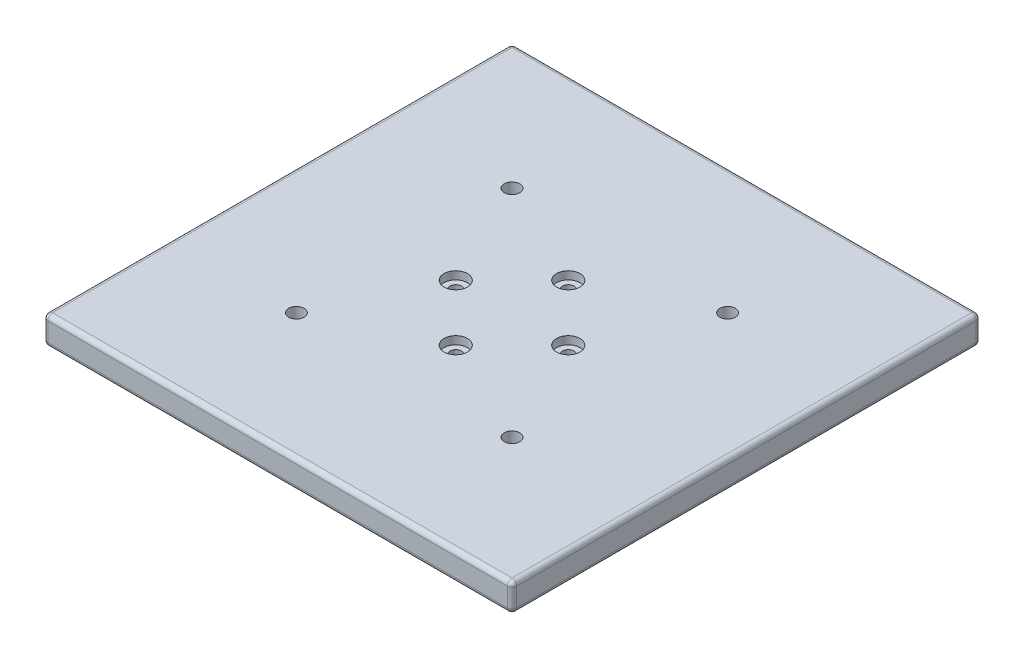
SolidWorks part; units mm, degrees
ref_plane "前视基准面" through (0, 0, 0) normal (0, 0, 1) x (1, 0, 0)
ref_plane "上视基准面" through (0, 0, 0) normal (0, 1, 0) x (1, 0, 0)
ref_plane "右视基准面" through (0, 0, 0) normal (1, 0, 0) x (0, 0, -1)
other "Configuration Table"
sketch "草图1" plane through (0, 0, 0) normal (0, 1, 0) x (1, 0, 0)
  line L1 (-88.6555, 21.1134) -> (11.3445, 21.1134)
  line L2 (-88.6555, 21.1134) -> (-88.6555, -78.8866)
  line L3 (-88.6555, -78.8866) -> (11.3445, -78.8866)
  line L4 (11.3445, 21.1134) -> (11.3445, -78.8866)
  dimension "D1" = 100
extrude "凸台-拉伸1" add sketch "草图1" along normal blind 6
sketch "草图2" plane through (0, 6, 0) normal (0, 1, 0) x (1, 0, 0)
  line L0 (-38.6555, 21.1134) -> (-38.6555, -78.8866) construction
  line L1 (11.3445, 21.1134) -> (-88.6555, 21.1134) construction
  line L2 (-88.6555, -78.8866) -> (11.3445, -78.8866) construction
  line L3 (-88.6555, -28.8866) -> (11.3445, -28.8866) construction
  line L4 (-88.6555, 21.1134) -> (-88.6555, -78.8866) construction
  line L5 (11.3445, -78.8866) -> (11.3445, 21.1134) construction
  point P12 (-38.6555, -16.8866)
  point P16 (-26.6555, -28.8866)
  point P18 (-38.6555, -40.8866)
  point P20 (-50.6555, -28.8866)
  dimension "D1" = 24
  dimension "D2" = 24
hole_wizard "M3 螺纹孔1" positions "3D草图1" profile "草图4" tap size "M3" standard "GB" end condition up to next
sketch3d "3D草图1"
  point P0 (-50.6555, 6, 28.8866)
  point P3 (-38.6555, 6, 40.8866)
  point P6 (-26.6555, 6, 28.8866)
  point P9 (-38.6555, 6, 16.8866)
sketch "草图4" plane through (-50.6555, 6, 28.8866) normal (1, 0, 0) x (0, 0, 1)
  line L0 (0, 0) -> (0, 6)
  line L1 (0, 6) -> (1.25, 6)
  line L2 (1.25, 6) -> (1.25, 0)
  line L5 (1.25, 0) -> (0, 0)
  line L11 (0, -6.35) -> (0, 107.95) construction
  dimension "通孔螺纹孔钻头直径" = 2.5
  dimension "通孔螺纹孔钻头深度" = 6
cosmetic thread "孔螺蚊线1" parameters "D2"=3
cosmetic thread "孔螺蚊线2" parameters "D2"=3
cosmetic thread "孔螺蚊线3" parameters "D2"=3
cosmetic thread "孔螺蚊线4" parameters "D2"=3
sketch "草图6" plane through (0, 6, 0) normal (0, 1, 0) x (1, 0, 0)
  circle A0 centre (-50.6555, -28.8866) radius 2.5
  circle A1 centre (-38.6555, -16.8866) radius 2.5
  circle A2 centre (-26.6555, -28.8866) radius 2.5
  circle A3 centre (-38.6555, -40.8866) radius 2.5
  dimension "D1" = 5
  dimension "D2" = 5
  dimension "D3" = 5
  dimension "D4" = 5
extrude "切除-拉伸1" cut sketch "草图6" against normal blind 1.7
sketch "草图7" plane through (0, 6, 0) normal (0, 1, 0) x (1, 0, 0)
  line L0 (-38.6555, 21.1134) -> (-38.6555, -78.8866) construction
  line L1 (-88.6555, -28.8866) -> (11.3445, -28.8866) construction
  line L2 (-88.6555, 21.1134) -> (-88.6555, -78.8866) construction
  point P0 (-61.6555, -5.8866)
  point P10 (-15.6555, -5.8866)
  point P11 (-15.6555, -51.8866)
  point P12 (-61.6555, -51.8866)
  dimension "D1" = 46
  dimension "D2" = 46
hole_wizard "M4 螺纹孔1" positions "草图7" profile "草图8" tap size "M4" standard "GB" end condition through all
sketch "草图8" plane through (-61.6555, 6, 5.8866) normal (1, 0, 0) x (0, 0, 1)
  line L0 (0, 0) -> (0, 6)
  line L1 (0, 6) -> (1.65, 6)
  line L2 (1.65, 6) -> (1.65, 0)
  line L5 (1.65, 0) -> (0, 0)
  line L11 (0, -6.35) -> (0, 107.95) construction
  dimension "通孔螺纹孔钻头直径" = 3.3
  dimension "通孔螺纹孔钻头深度" = 6
cosmetic thread "孔螺蚊线5" parameters "D2"=4
cosmetic thread "孔螺蚊线6" parameters "D2"=4
cosmetic thread "孔螺蚊线7" parameters "D2"=4
cosmetic thread "孔螺蚊线8" parameters "D2"=4
fillet "圆角1" radius 1 12 edges at (-88.6555, 6, 28.8866) (-88.6555, 0, 28.8866) (-38.6555, 6, -21.1134) (-88.6555, 3, -21.1134) (-38.6555, 0, -21.1134) (-88.6555, 3, 78.8866) (-38.6555, 6, 78.8866) (-38.6555, 0, 78.8866) (11.3445, 3, 78.8866) (11.3445, 6, 28.8866) (11.3445, 3, -21.1134) (11.3445, 0, 28.8866)
